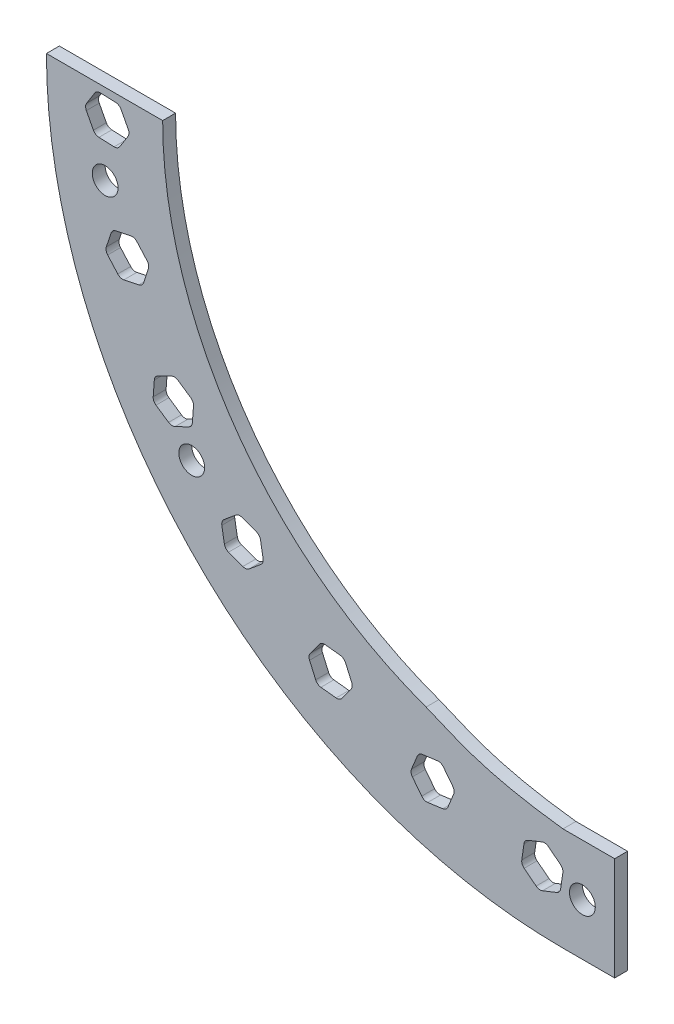
SolidWorks part; units mm, degrees
ref_plane "Front Plane" through (0, 0, 0) normal (0, 0, 1) x (1, 0, 0)
ref_plane "Top Plane" through (0, 0, 0) normal (0, 1, 0) x (1, 0, 0)
ref_plane "Right Plane" through (0, 0, 0) normal (1, 0, 0) x (0, 0, -1)
sketch "Layout" plane through (0, 0, 0) normal (0, 0, 1) x (1, 0, 0)
  line L0 (0, 0) -> (-76.2, 0) construction
  line L1 (-76.2, 0) -> (-203.2, 0) construction
  dimension "D1" = 76.2
  dimension "D2" = 127
sketch "Sketch1" plane through (0, 0, 0) normal (0, 0, 1) x (1, 0, 0)
  line L0 (0, 0) -> (-203.2, 0) construction
  line L1 (0, 0) -> (0, -203.2) construction
  line L2 (0, -203.2) -> (25.4, -203.2)
  line L3 (0, -254) -> (25.4, -254)
  line L4 (-254, 0) -> (-203.2, 0)
  line L5 (25.4, -203.2) -> (25.4, -254)
  arc A0 (-203.2, 0) -> (0, -203.2) centre (0, 0) ccw
  arc A1 (-254, 0) -> (0, -254) centre (0, 0) ccw
  dimension "D1" = 50.8
  dimension "D2" = 25.4
  dimension "D3" = 203.2
extrude "Boss-Extrude1" add sketch "Sketch1" along normal blind 6.35
sketch "Mid_Point_Sk" plane through (0, 0, 0) normal (0, 1, 0) x (1, 0, 0)
  line L0 (-254, 0) -> (-203.2, -6.35) construction
  line L1 (-254, -6.35) -> (-203.2, 0) construction
ref_point "Mid_Point"
ref_plane "Mid_Plane" through (0, 0, 3.175) normal (0, 0, 1) x (1, 0, 0)
sketch "Sketch2" plane through (0, 0, 6.35) normal (0, 0, 1) x (1, 0, 0)
  line L0 (0, 0) -> (-229.3095, 0) construction
  line L1 (0, 0) -> (-222.5647, -39.2442) construction
  line L2 (0, 0) -> (-173.1246, -145.2688) construction
  arc A0 (-222.5647, -39.2442) -> (-173.1246, -145.2688) centre (0, 0) ccw construction
  arc A1 (-222.5647, -39.2442) -> (-173.1246, -145.2688) centre (0, 0) ccw construction
  arc A2 (-228.8182, -40.3468) -> (-177.989, -149.3505) centre (0, 0) ccw
  arc A3 (-216.3112, -38.1415) -> (-168.2602, -141.1871) centre (0, 0) ccw
  arc A4 (-216.3112, -38.1415) -> (-228.8182, -40.3468) centre (-222.5647, -39.2442) ccw
  arc A5 (-177.989, -149.3505) -> (-168.2602, -141.1871) centre (-173.1246, -145.2688) ccw
  point P5 (-204.8238, -95.5109)
  dimension "D1" = 30
  dimension "D3" = 12.7
  dimension "D2" = 10
sketch "Sketch3" plane through (0, 0, 6.35) normal (0, 0, 1) x (1, 0, 0)
  line L0 (0, 0) -> (-225.1271, -39.696) construction
  line L1 (0, 0) -> (-182.5681, -137.5749) construction
  line L2 (-203.2, 0) -> (-254, 0) construction
  circle A1 centre (-182.5681, -137.5749) radius 6.35
  circle A3 centre (-225.1271, -39.696) radius 6.35
  dimension "D1" = 228.6
  dimension "D2" = 27
  dimension "D3" = 10
extrude "Cut-Extrude1" cut sketch "Sketch3" against normal up to next
sketch "Sketch4" plane through (0, 0, 6.35) normal (0, 0, 1) x (1, 0, 0)
  line L0 (0, -203.2) -> (0, -228.6) construction
  line L1 (0, -228.6) -> (9.525, -228.6) construction
  circle A1 centre (9.525, -228.6) radius 6.35
  dimension "D1" = 25.4
  dimension "D2" = 9.525
extrude "Cut-Extrude2" cut sketch "Sketch4" against normal up to next
sketch "Sketch5" plane through (0, 0, 6.35) normal (0, 0, 1) x (1, 0, 0)
  line L0 (0, 0) -> (-67.3267, -184.9785) construction
  line L2 (0, 0) -> (-196.85, 0) construction
  line L3 (-196.85, 0) -> (-203.2, 0)
  arc A0 (-67.3267, -184.9785) -> (-196.85, 0) centre (0, 0) cw
  arc A1 (-203.2, 0) -> (0, -203.2) centre (0, 0) ccw construction
  arc A2 (-203.2, 0) -> (0, -203.2) centre (0, 0) ccw
  spline S0 degree 3 poles (0, -203.2) (-42.7386, -198.0277) (-55.3777, -189.3302) (-67.3267, -184.9785) knots 0 0 0 0 1 1 1 1
  dimension "D1" = 70
  dimension "D2" = 196.85
extrude "Boss-Extrude2" add sketch "Sketch5" against normal up to surface (6.35 mm away) up to face at (15.875, -228.6, 0)
sketch "Sketch6" plane through (0, 0, 6.35) normal (0, 0, 1) x (1, 0, 0)
  line L0 (-204.5101, -63.4989) -> (-209.4922, -57.9153)
  line L1 (-217.9162, -21.638) -> (-213.9222, -15.3098)
  line L3 (-213.797, -12.1373) -> (-217.2803, -5.5142)
  line L4 (-219.9653, -3.8196) -> (-227.4427, -3.5247)
  line L5 (-230.2527, -5.0026) -> (-234.2468, -11.3308)
  line L6 (-234.3719, -14.5033) -> (-230.8886, -21.1264)
  line L7 (-228.2037, -22.821) -> (-220.7263, -23.1159)
  line L8 (-206.2085, -73.714) -> (-203.864, -66.6075)
  line L9 (-215.9042, -77.3506) -> (-208.5776, -75.8278)
  line L10 (-223.9014, -70.7722) -> (-218.9193, -76.3558)
  line L11 (-222.203, -60.5572) -> (-224.5475, -67.6636)
  line L12 (-212.5073, -56.9206) -> (-219.8339, -58.4434)
  line L13 (-183.0735, -111.0882) -> (-189.2584, -106.8757)
  line L14 (-182.2502, -121.4107) -> (-181.6945, -113.9481)
  line L15 (-190.7781, -127.2849) -> (-184.0375, -124.0348)
  line L16 (-200.1293, -122.8366) -> (-193.9443, -127.0491)
  line L17 (-200.9525, -112.5141) -> (-201.5082, -119.9767)
  line L18 (-192.4246, -106.6399) -> (-199.1652, -109.89)
  line L19 (-150.7607, -152.0779) -> (-157.781, -149.4868)
  line L20 (-147.4647, -161.8946) -> (-148.7309, -154.5193)
  line L21 (-154.3182, -169.6574) -> (-148.5641, -164.8732)
  line L22 (-164.4677, -167.6035) -> (-157.4474, -170.1946)
  line L23 (-167.7637, -157.7868) -> (-166.4975, -165.1621)
  line L24 (-160.9102, -150.024) -> (-166.6644, -154.8082)
  line L25 (-109.4915, -184.0329) -> (-116.9301, -183.2171)
  line L26 (-103.9185, -192.7606) -> (-106.9313, -185.9107)
  line L27 (-108.6904, -201.9508) -> (-104.2646, -195.9166)
  line L28 (-119.0353, -202.4133) -> (-111.5967, -203.2291)
  line L29 (-124.6083, -193.6856) -> (-121.5955, -200.5355)
  line L30 (-119.8364, -184.4954) -> (-124.2622, -190.5295)
  line L31 (-61.7176, -205.0547) -> (-69.1326, -206.0627)
  line L32 (-54.1987, -212.1749) -> (-58.7792, -206.2573)
  line L33 (-56.6055, -222.2466) -> (-53.771, -215.321)
  line L34 (-66.5313, -225.198) -> (-59.1163, -224.19)
  line L35 (-74.0502, -218.0778) -> (-69.4697, -223.9954)
  line L36 (-71.6433, -208.0061) -> (-74.4778, -214.9317)
  line L37 (-10.2771, -213.8945) -> (-17.228, -216.6664)
  line L38 (-1.259, -218.9843) -> (-7.135, -214.3506)
  line L39 (-1.1578, -229.339) -> (-0.0829, -221.9334)
  line L40 (-10.0747, -234.604) -> (-3.1238, -231.8321)
  line L41 (-19.0928, -229.5143) -> (-13.2168, -234.148)
  line L42 (-19.194, -219.1595) -> (-20.2688, -226.5651)
  line L43 (0, 0) -> (-213.797, -12.1373) construction
  line L44 (0, 0) -> (-204.5101, -63.4989) construction
  circle A0 centre (-224.0845, -13.3203) radius 9.6556 construction
  arc A1 (-209.4922, -57.9153) -> (-212.5073, -56.9206) centre (-211.8612, -60.0291) ccw
  arc A2 (-203.864, -66.6075) -> (-204.5101, -63.4989) centre (-206.8791, -65.6128) ccw
  arc A3 (-206.2085, -73.714) -> (-208.5776, -75.8278) centre (-209.2236, -72.7192) cw
  arc A4 (-218.9193, -76.3558) -> (-215.9042, -77.3506) centre (-216.5503, -74.242) ccw
  arc A5 (-224.5475, -67.6636) -> (-223.9014, -70.7722) centre (-221.5324, -68.6584) ccw
  arc A6 (-219.8339, -58.4434) -> (-222.203, -60.5572) centre (-219.1878, -61.5519) ccw
  arc A7 (-217.9162, -21.638) -> (-220.7263, -23.1159) centre (-220.6012, -19.9434) cw
  arc A8 (-230.8886, -21.1264) -> (-228.2037, -22.821) centre (-228.0786, -19.6485) ccw
  arc A9 (-234.2468, -11.3308) -> (-234.3719, -14.5033) centre (-231.5619, -13.0254) ccw
  arc A10 (-227.4427, -3.5247) -> (-230.2527, -5.0026) centre (-227.5678, -6.6972) ccw
  arc A11 (-217.2803, -5.5142) -> (-219.9653, -3.8196) centre (-220.0904, -6.9921) ccw
  arc A12 (-213.9222, -15.3098) -> (-213.797, -12.1373) centre (-216.6071, -13.6152) ccw
  arc A13 (-189.2584, -106.8757) -> (-192.4246, -106.6399) centre (-191.0457, -109.4999) ccw
  arc A14 (-181.6945, -113.9481) -> (-183.0735, -111.0882) centre (-184.8608, -113.7124) ccw
  arc A15 (-182.2502, -121.4107) -> (-184.0375, -124.0348) centre (-185.4164, -121.1749) cw
  arc A16 (-193.9443, -127.0491) -> (-190.7781, -127.2849) centre (-192.157, -124.425) ccw
  arc A17 (-201.5082, -119.9767) -> (-200.1293, -122.8366) centre (-198.342, -120.2125) ccw
  arc A18 (-199.1652, -109.89) -> (-200.9525, -112.5141) centre (-197.7863, -112.7499) ccw
  arc A19 (-157.781, -149.4868) -> (-160.9102, -150.024) centre (-158.8804, -152.4654) ccw
  arc A20 (-148.7309, -154.5193) -> (-150.7607, -152.0779) centre (-151.8601, -155.0565) ccw
  arc A21 (-147.4647, -161.8946) -> (-148.5641, -164.8732) centre (-150.5939, -162.4318) cw
  arc A22 (-157.4474, -170.1946) -> (-154.3182, -169.6574) centre (-156.348, -167.216) ccw
  arc A23 (-166.4975, -165.1621) -> (-164.4677, -167.6035) centre (-163.3683, -164.6249) ccw
  arc A24 (-166.6644, -154.8082) -> (-167.7637, -157.7868) centre (-164.6345, -157.2496) ccw
  arc A25 (-116.9301, -183.2171) -> (-119.8364, -184.4954) centre (-117.2762, -186.3732) ccw
  arc A26 (-106.9313, -185.9107) -> (-109.4915, -184.0329) centre (-109.8376, -187.1889) ccw
  arc A27 (-103.9185, -192.7606) -> (-104.2646, -195.9166) centre (-106.8248, -194.0389) cw
  arc A28 (-111.5967, -203.2291) -> (-108.6904, -201.9508) centre (-111.2506, -200.073) ccw
  arc A29 (-121.5955, -200.5355) -> (-119.0353, -202.4133) centre (-118.6892, -199.2572) ccw
  arc A30 (-124.2622, -190.5295) -> (-124.6083, -193.6856) centre (-121.702, -192.4073) ccw
  arc A31 (-69.1326, -206.0627) -> (-71.6433, -208.0061) centre (-68.7049, -209.2088) ccw
  arc A32 (-58.7792, -206.2573) -> (-61.7176, -205.0547) centre (-61.2899, -208.2008) ccw
  arc A33 (-54.1987, -212.1749) -> (-53.771, -215.321) centre (-56.7094, -214.1183) cw
  arc A34 (-59.1163, -224.19) -> (-56.6055, -222.2466) centre (-59.544, -221.0439) ccw
  arc A35 (-69.4697, -223.9954) -> (-66.5313, -225.198) centre (-66.959, -222.0519) ccw
  arc A36 (-74.4778, -214.9317) -> (-74.0502, -218.0778) centre (-71.5394, -216.1344) ccw
  arc A37 (-17.228, -216.6664) -> (-19.194, -219.1595) centre (-16.0519, -219.6156) ccw
  arc A38 (-7.135, -214.3506) -> (-10.2771, -213.8945) centre (-9.101, -216.8437) ccw
  arc A39 (-1.259, -218.9843) -> (-0.0829, -221.9334) centre (-3.225, -221.4774) cw
  arc A40 (-3.1238, -231.8321) -> (-1.1578, -229.339) centre (-4.2999, -228.883) ccw
  arc A41 (-13.2168, -234.148) -> (-10.0747, -234.604) centre (-11.2508, -231.6549) ccw
  arc A42 (-20.2688, -226.5651) -> (-19.0928, -229.5143) centre (-17.1268, -227.0212) ccw
  point P12 (0, 0)
  point P75 (-212.9438, -13.7597)
  dimension "D1" = 14
  dimension "D2" = 3.175
extrude "Cut-Extrude3" cut sketch "Sketch6" against normal through all
